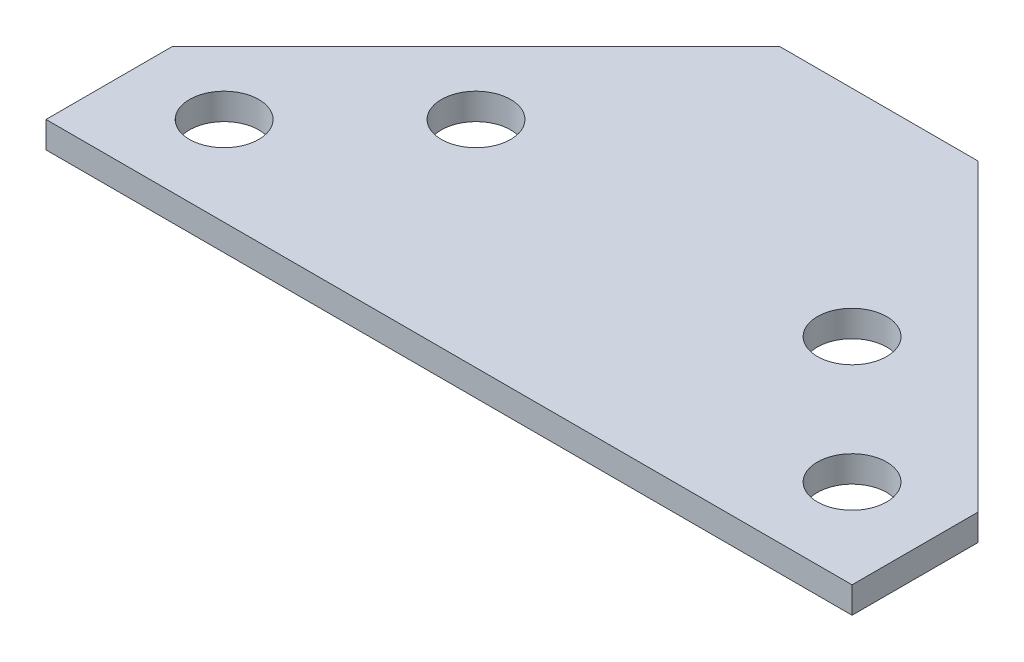
SolidWorks part; units mm, degrees
material "AISI 1020"
ref_plane "Спереди" through (0, 0, 0) normal (0, 0, 1) x (1, 0, 0)
ref_plane "Сверху" through (0, 0, 0) normal (0, 1, 0) x (1, 0, 0)
ref_plane "Справа" through (0, 0, 0) normal (1, 0, 0) x (0, 0, -1)
sketch "Эскиз1" plane through (0, 0, 0) normal (0, 1, 0) x (1, 0, 0)
  line L0 (-61.0919, 0) -> (61.0919, 0)
  line L1 (61.0919, 0) -> (61.0919, 19.0919)
  line L2 (61.0919, 19.0919) -> (15, 65.1838)
  line L3 (15, 65.1838) -> (-15, 65.1838)
  line L4 (-15, 65.1838) -> (-61.0919, 19.0919)
  line L5 (-61.0919, 19.0919) -> (-61.0919, 0)
  line L6 (0, 65.1838) -> (0, 0) construction
  line L7 (-15, 65.1838) -> (-15, 0) construction
  line L8 (-28.5, 32.5919) -> (-47.5919, 13.5) construction
  circle A0 centre (-47.5919, 13.5) radius 13.5 construction
  circle A1 centre (-28.5, 32.5919) radius 13.5 construction
  circle A2 centre (-28.5, 32.5919) radius 5.25
  circle A3 centre (-47.5919, 13.5) radius 5.25
  circle A4 centre (47.5919, 13.5) radius 5.25
  circle A5 centre (28.5, 32.5919) radius 5.25
  point P10 (0, 0)
  point P12 (0, 65.1838)
  dimension "D2" = 27
  dimension "D3" = 10.5
  dimension "D1" = 30
  dimension "D4" = 45
base flange "Базовая кромка1" sketch "Эскиз1" thickness 4 reverse thickness direction no parameters "D1"=0.75
sketch "Сгиб-Линии1" plane through (0, 0, 0) normal (0, 1, 0) x (1, 0, 0)
sketch "Граничная рамка1" plane through (0, 0, 0) normal (0, 1, 0) x (1, 0, 0)
sheet metal parameters "Листовой металл3" thickness 4 parameters "D1"=0.75
flat pattern "Развертка3"
sketch "Сгиб-Линии2" plane through (0, 0, 0) normal (0, 1, 0) x (1, 0, 0)
sketch3d "Граничная рамка2"
  line L0 (61.0919, 0, 0) -> (-61.0919, 0, 0) construction
  line L1 (61.0919, 65.1838, 0) -> (-61.0919, 65.1838, 0) construction
  line L2 (61.0919, 0, 0) -> (61.0919, 65.1838, 0) construction
  line L3 (-61.0919, 0, 0) -> (-61.0919, 65.1838, 0) construction
